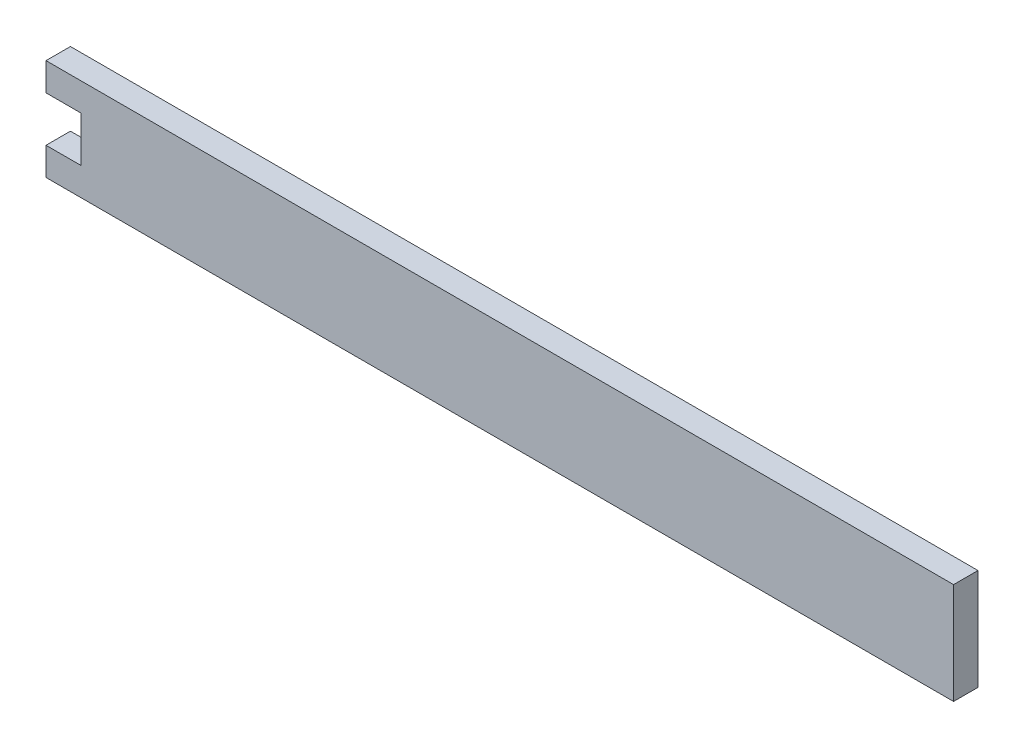
SolidWorks part; units mm, degrees
material "Pino"
ref_plane "Alzado" through (0, 0, 0) normal (0, 0, 1) x (1, 0, 0)
ref_plane "Planta" through (0, 0, 0) normal (0, 1, 0) x (1, 0, 0)
ref_plane "Vista lateral" through (0, 0, 0) normal (1, 0, 0) x (0, 0, -1)
sketch "Croquis1" plane through (0, 0, 0) normal (0, 0, 1) x (1, 0, 0)
  line L1 (-650, -72.5) -> (650, -72.5)
  line L2 (-650, -72.5) -> (-650, 72.5)
  line L3 (-650, 72.5) -> (650, 72.5)
  line L4 (650, -72.5) -> (650, 72.5)
  line L5 (-650, -72.5) -> (650, 72.5) construction
  line L6 (-650, 72.5) -> (650, -72.5) construction
  point P0 (0, 0)
  dimension "D1" = 1300
  dimension "D2" = 145
extrude "Saliente-Extruir1" add sketch "Croquis1" along normal blind 35
sketch "Sketch1" plane through (-650, 0, 0) normal (-1, 0, 0) x (0, 0, 1)
  line L0 (0, 72.5) -> (0, -72.5) construction
  line L1 (0, -32.5) -> (35, -32.5)
  line L2 (0, -32.5) -> (0, 32.5)
  line L3 (0, 32.5) -> (35, 32.5)
  line L4 (35, -32.5) -> (35, 32.5)
  line L5 (35, 72.5) -> (35, -72.5) construction
  line L6 (35, 72.5) -> (0, 72.5) construction
  line L7 (35, -72.5) -> (0, -72.5) construction
  dimension "D1" = 40
  dimension "D2" = 40
extrude "Cut-Extrude1" cut sketch "Sketch1" against normal blind 50
